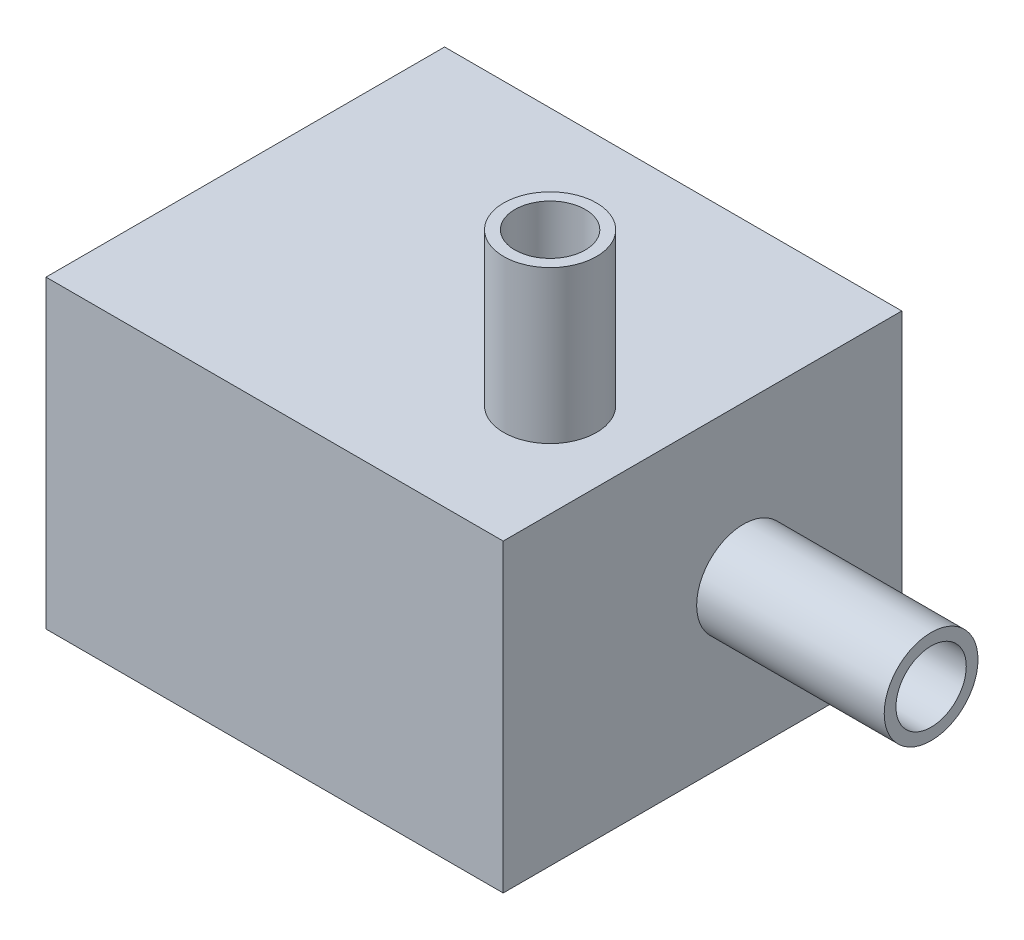
SolidWorks part; units mm, degrees
ref_plane "Front Plane" through (0, 0, 0) normal (0, 0, 1) x (1, 0, 0)
ref_plane "Top Plane" through (0, 0, 0) normal (0, 1, 0) x (1, 0, 0)
ref_plane "Right Plane" through (0, 0, 0) normal (1, 0, 0) x (0, 0, -1)
sketch "Sketch1" plane through (0, 0, 0) normal (0, 1, 0) x (1, 0, 0)
  line L1 (-19.5, -17) -> (19.5, -17)
  line L2 (-19.5, -17) -> (-19.5, 17)
  line L3 (-19.5, 17) -> (19.5, 17)
  line L4 (19.5, -17) -> (19.5, 17)
  line L5 (-19.5, -17) -> (19.5, 17) construction
  line L6 (-19.5, 17) -> (19.5, -17) construction
  point P0 (0, 0)
  dimension "D1" = 39
  dimension "D2" = 34
extrude "Boss-Extrude1" add sketch "Sketch1" along normal blind 26
sketch "Sketch2" plane through (0, 26, 0) normal (0, 1, 0) x (1, 0, 0)
  line L0 (-19.5, -17) -> (19.5, -17) construction
  line L1 (19.5, -17) -> (19.5, 17) construction
  circle A0 centre (11.5, -5) radius 3.9602
  dimension "D1" = 12
  dimension "D2" = 8
extrude "Boss-Extrude2" add sketch "Sketch2" along normal blind 13
sketch "Sketch3" plane through (0, 39, 0) normal (0, 1, 0) x (1, 0, 0)
  circle A0 centre (11.5, -5) radius 3
  dimension "D1" = 6
extrude "Cut-Extrude1" cut sketch "Sketch3" against normal blind 13
sketch "Sketch4" plane through (19.5, 0, 0) normal (1, 0, 0) x (0, 0, -1)
  line L0 (-17, 0) -> (17, 0) construction
  line L1 (17, 26) -> (17, 0) construction
  circle A0 centre (3.5, 13) radius 4
  dimension "D3" = 8
  dimension "D1" = 13
  dimension "D2" = 13.5
extrude "Boss-Extrude3" add sketch "Sketch4" along normal blind 16
sketch "Sketch5" plane through (35.5, 0, 0) normal (1, 0, 0) x (0, 0, -1)
  circle A0 centre (3.5, 13) radius 3
  dimension "D1" = 6
extrude "Cut-Extrude2" cut sketch "Sketch5" against normal blind 16
